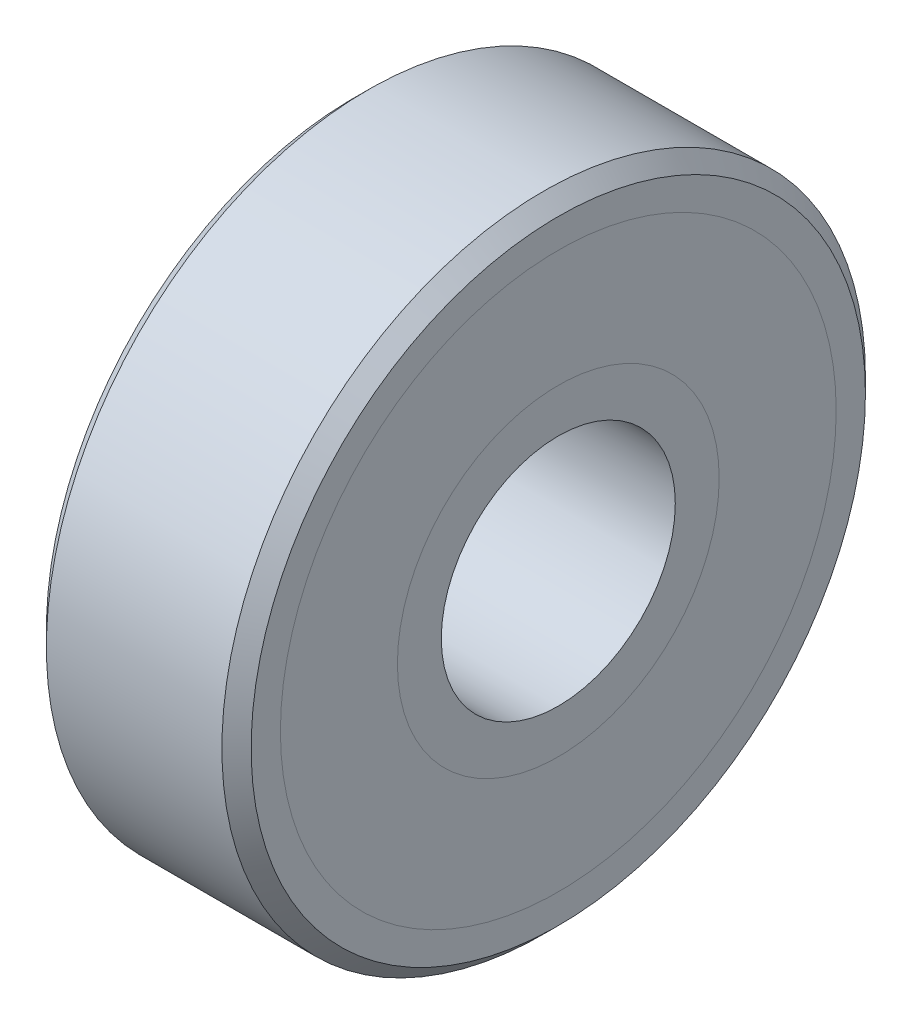
SolidWorks part; units mm, degrees
ref_plane "Front" through (0, 0, 0) normal (0, 0, 1) x (1, 0, 0)
ref_plane "Top" through (0, 0, 0) normal (0, 1, 0) x (1, 0, 0)
ref_plane "Right" through (0, 0, 0) normal (1, 0, 0) x (0, 0, -1)
sketch "Sketch1" plane through (0, 0, 0) normal (1, 0, 0) x (0, 0, -1)
  circle A0 centre (0, 0) radius 11
  circle A1 centre (0, 0) radius 4
  dimension "D1" = 22
  dimension "D2" = 8
extrude "Boss-Extrude1" add sketch "Sketch1" along normal mid plane 7
sketch "Sketch2" plane through (3.5, 0, 0) normal (1, 0, 0) x (0, 0, -1)
  circle A0 centre (0, 0) radius 5.5
  circle A1 centre (0, 0) radius 9.5
  circle A2 centre (0, 0) radius 11 construction
  circle A3 centre (0, 0) radius 4 construction
  dimension "D1" = 1.5
  dimension "D2" = 1.5
split line "Split Line1"
chamfer "Chamfer1" distance 0.5 angle 45 2 edges at (3.5, 0, -11) (-3.5, 0, -11)
ref_axis "Axis1" through (3.5, 0, 0) along (-1, 0, 0)
